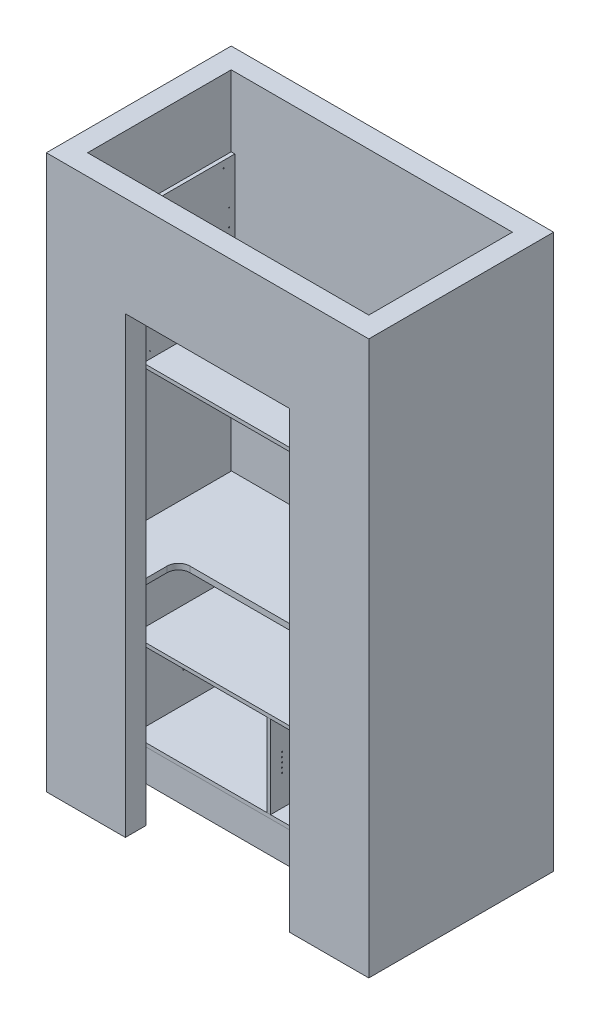
SolidWorks part; units mm, degrees
ref_plane "Front" through (0, 0, 0) normal (0, 0, 1) x (1, 0, 0)
ref_plane "Top" through (0, 0, 0) normal (0, 1, 0) x (1, 0, 0)
ref_plane "Right" through (0, 0, 0) normal (1, 0, 0) x (0, 0, -1)
sketch "Sketch1" plane through (0, 0, 0) normal (0, 1, 0) x (1, 0, 0)
  line L0 (-90, 90) -> (1317.5, 90)
  line L1 (0, 0) -> (1227.5, 0)
  line L2 (0, 0) -> (0, -627)
  line L3 (0, -627) -> (255, -627)
  line L4 (1227.5, 0) -> (1227.5, -627)
  line L5 (1317.5, 90) -> (1317.5, -717)
  line L6 (-90, -717) -> (255, -717)
  line L7 (-90, 90) -> (-90, -717)
  line L8 (255, -627) -> (255, -717)
  line L9 (972.5, -627) -> (972.5, -717)
  line L10 (972.5, -717) -> (1317.5, -717)
  line L11 (972.5, -627) -> (1227.5, -627)
  line L12 (-90, -717) -> (1317.5, -717) construction
  line L13 (255, -627) -> (972.5, -627)
  line L14 (0, -627) -> (1227.5, -627) construction
  line L15 (255, -717) -> (972.5, -717)
  dimension "D1" = 1227.5
  dimension "D2" = 627
  dimension "D4" = 255
  dimension "D5" = 255
  dimension "D3" = 90
extrude "Boss-Extrude1" add sketch "Sketch1" along normal blind 2416 contours L11 L9 L10 L5 L0 L7 L6 L8 L3 L2 L1 L4 | L8 L15 L9 L13 region at (613.75, 0, -73.7756) region at (613.75, 0, 672)
sketch "Sketch2" plane through (0, 0, 717) normal (0, 0, 1) x (1, 0, 0)
  line L0 (-90, 0) -> (1317.5, 0) construction
  line L1 (255, 0) -> (972.5, 0)
  line L2 (255, 0) -> (255, 1980)
  line L3 (255, 1980) -> (972.5, 1980)
  line L4 (972.5, 0) -> (972.5, 1980)
  line L5 (0, 2416) -> (0, 0) construction
  line L6 (1227.5, 2416) -> (1227.5, 0) construction
  dimension "D1" = 255
  dimension "D2" = 255
  dimension "D3" = 1980
  dimension "D4" = 717.5
extrude "Cut-Extrude1" cut sketch "Sketch2" against normal blind 100
sketch "Sketch4" plane through (0, 0, 0) normal (0, 0, 1) x (1, 0, 0)
  line L0 (1227.5, 2416) -> (1227.5, 0) construction
  line L5 (0, 120) -> (1227.5, 120)
  line L7 (16, 136) -> (1211.5, 136)
  line L9 (16, 513.5) -> (605.75, 513.5)
  line L11 (16, 497.5) -> (605.75, 497.5)
  line L13 (16, 875) -> (1211.5, 875)
  line L15 (16, 900) -> (1211.5, 900)
  line L21 (16, 1500) -> (1211.5, 1500)
  line L23 (16, 1516) -> (1211.5, 1516)
  line L25 (16, 1766) -> (1211.5, 1766)
  line L27 (16, 1782) -> (1211.5, 1782)
  line L37 (621.75, 513.5) -> (1211.5, 513.5)
  line L38 (621.75, 497.5) -> (1211.5, 497.5)
  line L39 (16, 1500) -> (0, 1500)
  line L40 (0, 120) -> (16, 120)
  line L41 (0, 120) -> (0, 2320)
  line L42 (598, 120) -> (613.75, 120)
  line L43 (605.75, 136) -> (605.75, 875)
  line L44 (605.75, 875) -> (614, 875)
  line L46 (614, 875) -> (621.75, 875)
  line L48 (613.75, 120) -> (630, 120)
  line L49 (621.75, 875) -> (621.75, 136)
  line L50 (0, 2320) -> (16, 2320)
  line L51 (16, 120) -> (16, 2320)
  line L52 (1211.5, 1500) -> (1227.5, 1500)
  line L54 (1227.5, 2320) -> (1227.5, 120)
  line L56 (1211.5, 2320) -> (1211.5, 120)
  line L57 (613.75, 136) -> (613.75, 171.2625) construction
  line L58 (1211.5, 2320) -> (1227.5, 2320)
  line L59 (-90, 0) -> (255, 0) construction
  line L60 (310.875, 513.5) -> (310.875, 875) construction
  line L61 (310.875, 497.5) -> (310.875, 136) construction
  dimension "D2" = 120
  dimension "D4" = 16
  dimension "D5" = 16
  dimension "D6" = 8
  dimension "D3" = 25
  dimension "D7" = 1500
  dimension "D8" = 250
  dimension "D9" = 16
  dimension "D10" = 2200
  dimension "D11" = 16
  dimension "D12" = 16
  dimension "D13" = 16
  dimension "D14" = 16
  dimension "D15" = 900
sketch "Sketch6" plane through (0, 0, 0) normal (0, 0, 1) x (1, 0, 0)
  line L0 (0, 120) -> (0, 2320) construction
  line L13 (16, 875) -> (0, 875)
  line L14 (16, 875) -> (16, 136)
  line L15 (16, 136) -> (0, 136)
  line L16 (0, 875) -> (0, 136)
  line L17 (16, 136) -> (1211.5, 136) construction
  line L18 (1227.5, 2320) -> (1227.5, 120) construction
  line L19 (1211.5, 875) -> (1227.5, 875)
  line L20 (1211.5, 875) -> (1211.5, 136)
  line L21 (1211.5, 136) -> (1227.5, 136)
  line L22 (1227.5, 875) -> (1227.5, 136)
  line L24 (605.75, 497.5) -> (621.75, 497.5)
  line L25 (605.75, 497.5) -> (605.75, 136)
  line L26 (605.75, 136) -> (621.75, 136)
  line L27 (621.75, 497.5) -> (621.75, 136)
extrude "Boss-Extrude2" add sketch "Sketch6" along normal blind 450 separate body
sketch "Sketch7" plane through (0, 0, 0) normal (0, 0, 1) x (1, 0, 0)
  line L0 (1227.5, 2320) -> (1227.5, 120) construction
  line L1 (0, 120) -> (1227.5, 120)
  line L2 (0, 120) -> (0, 136)
  line L3 (0, 136) -> (1227.5, 136)
  line L4 (1227.5, 120) -> (1227.5, 136)
  line L6 (16, 497.5) -> (16, 513.5)
  line L7 (16, 513.5) -> (1211.5, 513.5)
  line L9 (16, 497.5) -> (1211.5, 497.5)
  line L12 (1211.5, 497.5) -> (1211.5, 513.5)
  line L13 (0, 875) -> (1227.5, 875)
  line L14 (0, 875) -> (0, 900)
  line L15 (0, 900) -> (1227.5, 900)
  line L16 (1227.5, 875) -> (1227.5, 900)
  line L17 (16, 900) -> (1211.5, 900) construction
  line L19 (1211.5, 2320) -> (1211.5, 120) construction
  line L20 (16, 120) -> (16, 2320) construction
extrude "Boss-Extrude3" add sketch "Sketch7" along normal blind 450 separate body
sketch "Sketch8" plane through (0, 0, 0) normal (0, 0, 1) x (1, 0, 0)
  line L0 (0, 120) -> (0, 2320) construction
  line L1 (16, 1516) -> (0, 1516)
  line L2 (16, 1516) -> (16, 2106)
  line L3 (16, 2106) -> (0, 2106)
  line L4 (0, 1516) -> (0, 2106)
  line L5 (1227.5, 2320) -> (1227.5, 120) construction
  line L6 (1211.5, 1516) -> (1227.5, 1516)
  line L7 (1211.5, 1516) -> (1211.5, 2106)
  line L8 (1211.5, 2106) -> (1227.5, 2106)
  line L9 (1227.5, 1516) -> (1227.5, 2106)
  line L10 (16, 120) -> (16, 2320) construction
  dimension "D1" = 590
extrude "Boss-Extrude4" add sketch "Sketch8" along normal blind 400 separate body
sketch "Sketch9" plane through (0, 0, 0) normal (0, 0, 1) x (1, 0, 0)
  line L0 (1226.5, 1516) -> (1226.5, 1500)
  line L1 (16, 1782) -> (1211.5, 1782)
  line L2 (16, 1782) -> (16, 1766)
  line L3 (16, 1766) -> (1211.5, 1766)
  line L4 (1211.5, 1782) -> (1211.5, 1766)
  line L5 (1, 1516) -> (1226.5, 1516)
  line L6 (0, 1516) -> (0, 1500) construction
  line L7 (1, 1500) -> (1226.5, 1500)
  line L8 (1227.5, 1516) -> (1227.5, 1500) construction
  line L9 (1, 1516) -> (1, 1500)
  dimension "D1" = 1
  dimension "D2" = 1
extrude "Boss-Extrude5" add sketch "Sketch9" along normal blind 400 separate body
sketch "Sketch11" plane through (0, 900, 0) normal (0, 1, 0) x (1, 0, 0)
  line L0 (0, -450) -> (0, -627)
  line L1 (0, -627) -> (220, -627)
  line L2 (0, -627) -> (1227.5, -627) construction
  line L3 (220, -627) -> (220, -450)
  line L4 (1227.5, -450) -> (0, -450) construction
  line L5 (613.75, 90) -> (613.75, 254.9806) construction
  line L6 (-90, 90) -> (1317.5, 90) construction
  line L7 (0, -450) -> (220, -450)
  line L8 (1227.5, -450) -> (1007.5, -450)
  line L9 (1007.5, -627) -> (1007.5, -450)
  line L10 (1227.5, -627) -> (1007.5, -627)
  line L11 (1227.5, -450) -> (1227.5, -627)
  dimension "D1" = 220
extrude "Boss-Extrude6" add sketch "Sketch11" against normal up to surface (25 mm away) up to face at (613.75, 875, 225)
fillet "Fillet1" radius 50 2 edges at (220, 887.5, 450) (1007.5, 887.5, 450)
sketch "Sketch18" plane through (0, 120, 0) normal (0, -1, 0) x (1, 0, 0)
  line L0 (16, 0) -> (1211.5, 0) construction
  line L1 (0, 627) -> (1.25, 627)
  line L2 (0, 627) -> (0, 0)
  line L3 (0, 0) -> (1.25, 0)
  line L4 (1.25, 627) -> (1.25, 0)
  line L5 (1.25, 73.7952) -> (1226.25, 73.7952) construction
  line L6 (1227.5, 627) -> (1226.25, 627)
  line L7 (1227.5, 627) -> (1227.5, 0)
  line L8 (1227.5, 0) -> (1226.25, 0)
  line L9 (1226.25, 627) -> (1226.25, 0)
  line L10 (613.75, 73.7952) -> (613.75, -90) construction
  line L11 (-90, -90) -> (1317.5, -90) construction
  dimension "D1" = 1225
extrude "Cut-Extrude5" cut sketch "Sketch18" against normal through all
hole_wizard "Ø2.0 (2) Diameter Hole1" positions "Sketch20" profile "Sketch21" hole size "Ø2.0" standard "ISO"
sketch "Sketch20" plane through (0, 120, 0) normal (0, -1, 0) x (-1, 0, 0)
  line L1 (-645.75, -32) -> (-581.75, -32)
  line L2 (-645.75, -32) -> (-645.75, -96)
  line L3 (-645.75, -96) -> (-581.75, -96)
  line L4 (-581.75, -32) -> (-581.75, -96)
  line L7 (-613.75, -32) -> (-613.75, 0) construction
  line L8 (-1.25, 0) -> (-1226.25, 0) construction
  line L10 (0, 0) -> (-1227.5, 0) construction
  line L12 (-1176.25, -336.5) -> (-1112.25, -336.5)
  line L13 (-1176.25, -336.5) -> (-1176.25, -400.5)
  line L14 (-1176.25, -400.5) -> (-1112.25, -400.5)
  line L15 (-1112.25, -336.5) -> (-1112.25, -400.5)
  line L17 (-645.75, -336.5) -> (-581.75, -336.5)
  line L18 (-645.75, -336.5) -> (-645.75, -400.5)
  line L19 (-645.75, -400.5) -> (-581.75, -400.5)
  line L20 (-581.75, -336.5) -> (-581.75, -400.5)
  line L22 (-115.25, -336.5) -> (-51.25, -336.5)
  line L23 (-115.25, -336.5) -> (-115.25, -400.5)
  line L24 (-115.25, -400.5) -> (-51.25, -400.5)
  line L25 (-51.25, -336.5) -> (-51.25, -400.5)
  line L26 (-1226.25, -450) -> (-1226.25, 0) construction
  line L27 (-1.25, 0) -> (-1.25, -450) construction
  line L28 (-270, -450) -> (-957.5, -450) construction
  point P0 (-645.75, -32)
  point P2 (-581.75, -32)
  point P4 (-581.75, -96)
  point P6 (-645.75, -96)
  point P82 (-645.75, -400.5)
  point P84 (-645.75, -336.5)
  point P86 (-581.75, -336.5)
  point P88 (-581.75, -400.5)
  point P90 (-51.25, -400.5)
  point P92 (-51.25, -336.5)
  point P94 (-115.25, -336.5)
  point P96 (-115.25, -400.5)
  point P98 (-1176.25, -336.5)
  point P100 (-1112.25, -336.5)
  point P102 (-1112.25, -400.5)
  point P104 (-1176.25, -400.5)
  dimension "D1" = 50
  dimension "D2" = 64
  dimension "D3" = 50
  dimension "D4" = 49.5
  dimension "D5" = 64
  dimension "D6" = 32
sketch "Sketch21" plane through (645.75, 120, 32) normal (1, 0, 0) x (0, 0, -1)
  line L0 (0, 0) -> (0, 10.6009)
  line L1 (0, 10.6009) -> (1, 10)
  line L2 (1, 10) -> (1, 0)
  line L5 (1, 0) -> (0, 0)
  line L10 (0, 10.6009) -> (-1, 10) construction
  line L11 (0, -6.35) -> (0, 107.95) construction
  dimension "Hole Dia." = 2
  dimension "Hole Depth" = 10
  dimension "Drill Angle" = 118
hole_wizard "Ø2.0 (2) Diameter Hole2" positions "Sketch22" profile "Sketch23" hole size "Ø2.0" standard "ISO"
sketch "Sketch22" plane through (0, 120, 0) normal (0, -1, 0) x (-1, 0, 0)
  line L0 (-1219.5, -15) -> (-1219.5, -435) construction
  line L2 (-1227.5, 0) -> (-1227.5, -627) construction
  line L3 (0, 0) -> (0, -627) construction
  line L4 (-1.25, -450) -> (-1226.25, -450) construction
  line L5 (0, 0) -> (-1227.5, 0) construction
  line L6 (-613.75, -435) -> (-613.75, -450) construction
  line L7 (-270, -450) -> (-957.5, -450) construction
  point P0 (-1219.5, -435)
  point P2 (-1219.5, -225)
  point P4 (-1219.5, -15)
  point P6 (-613.75, -15)
  point P8 (-613.75, -225)
  point P10 (-613.75, -435)
  point P12 (-8, -15)
  point P14 (-8, -225)
  point P16 (-8, -435)
  dimension "D1" = 8
  dimension "D2" = 8
  dimension "D3" = 15
  dimension "D4" = 15
sketch "Sketch23" plane through (1219.5, 120, 435) normal (1, 0, 0) x (0, 0, -1)
  line L0 (0, 0) -> (0, 10.6009)
  line L1 (0, 10.6009) -> (1, 10)
  line L2 (1, 10) -> (1, 0)
  line L5 (1, 0) -> (0, 0)
  line L10 (0, 10.6009) -> (-1, 10) construction
  line L11 (0, -6.35) -> (0, 107.95) construction
  dimension "Hole Dia." = 2
  dimension "Hole Depth" = 10
  dimension "Drill Angle" = 118
sketch "Sketch24" plane through (0, 120, 0) normal (0, -1, 0) x (1, 0, 0)
  circle A0 centre (8, 435) radius 2.5
  circle A1 centre (8, 225) radius 2.5
  circle A2 centre (8, 15) radius 2.5
  circle A3 centre (613.75, 435) radius 2.5
  circle A4 centre (613.75, 225) radius 2.5
  circle A5 centre (613.75, 15) radius 2.5
  circle A6 centre (1219.5, 15) radius 2.5
  circle A7 centre (1219.5, 225) radius 2.5
  circle A8 centre (1219.5, 435) radius 2.5
  dimension "D1" = 5
extrude "Cut-Extrude6" cut sketch "Sketch24" against normal blind 1
sketch "Sketch25" plane through (16, 0, 0) normal (1, 0, 0) x (0, 0, -1)
  line L0 (-450, 497.5) -> (0, 497.5) construction
  line L1 (-450, 497.5) -> (0, 497.5) construction
  line L2 (-400, 497.5) -> (-50, 497.5) construction
  circle A0 centre (-400, 497.5) radius 2.5
  circle A1 centre (-50, 497.5) radius 2.5
  circle A2 centre (-225, 497.5) radius 2.5
  dimension "D1" = 5
  dimension "D2" = 350
extrude "Cut-Extrude7" cut sketch "Sketch25" against normal through all both and the other way through all
sketch "Sketch26" plane through (16, 0, 0) normal (1, 0, 0) x (0, 0, -1)
  line L0 (-400, 497.5) -> (-50, 497.5) construction
  circle A0 centre (-400, 308.75) radius 2.5
  circle A1 centre (-225, 308.75) radius 2.5
  circle A2 centre (-50, 308.75) radius 2.5
  circle A3 centre (-400, 497.5) radius 2.5 construction
  circle A4 centre (-400, 328.75) radius 2.5
  circle A5 centre (-225, 328.75) radius 2.5
  circle A6 centre (-50, 328.75) radius 2.5
  circle A7 centre (-400, 348.75) radius 2.5
  circle A8 centre (-225, 348.75) radius 2.5
  circle A9 centre (-50, 348.75) radius 2.5
  circle A10 centre (-400, 288.75) radius 2.5
  circle A11 centre (-225, 288.75) radius 2.5
  circle A12 centre (-50, 288.75) radius 2.5
  circle A13 centre (-400, 268.75) radius 2.5
  circle A14 centre (-225, 268.75) radius 2.5
  circle A15 centre (-50, 268.75) radius 2.5
  dimension "D1" = 188.75
  dimension "D2" = 3
  dimension "D3" = 3
extrude "Cut-Extrude8" cut sketch "Sketch26" against normal through all both and the other way through all
sketch "Sketch34" plane through (0, 497.5, 0) normal (0, -1, 0) x (1, 0, 0)
  line L0 (16, 450) -> (16, 0) construction
  line L1 (16, 403) -> (39.6625, 403)
  line L2 (16, 403) -> (16, 397)
  line L3 (16, 397) -> (39.6625, 397)
  line L4 (41.25, 401.4125) -> (41.25, 398.5875)
  line L15 (16, 400) -> (41.25, 400) construction
  line L16 (1.25, 0) -> (1.25, 450) construction
  line L17 (0, 400) -> (16, 400) construction
  line L18 (16, 228) -> (39.6625, 228)
  line L19 (16, 228) -> (16, 222)
  line L20 (16, 222) -> (39.6625, 222)
  line L21 (41.25, 226.4125) -> (41.25, 223.5875)
  line L22 (16, 225) -> (41.25, 225) construction
  line L23 (16, 53) -> (39.6625, 53)
  line L24 (16, 53) -> (16, 47)
  line L25 (16, 47) -> (39.6625, 47)
  line L26 (41.25, 51.4125) -> (41.25, 48.5875)
  line L27 (16, 50) -> (41.25, 50) construction
  line L28 (613.75, 435) -> (613.75, 225) construction
  line L29 (1211.5, 50) -> (1186.25, 50) construction
  line L30 (1211.5, 225) -> (1186.25, 225) construction
  line L31 (1211.5, 400) -> (1186.25, 400) construction
  line L32 (1186.25, 51.4125) -> (1186.25, 48.5875)
  line L33 (1211.5, 47) -> (1187.8375, 47)
  line L34 (1211.5, 53) -> (1211.5, 47)
  line L35 (1211.5, 53) -> (1187.8375, 53)
  line L36 (1186.25, 226.4125) -> (1186.25, 223.5875)
  line L37 (1211.5, 222) -> (1187.8375, 222)
  line L38 (1211.5, 228) -> (1211.5, 222)
  line L39 (1211.5, 228) -> (1187.8375, 228)
  line L40 (1186.25, 401.4125) -> (1186.25, 398.5875)
  line L41 (1211.5, 397) -> (1187.8375, 397)
  line L42 (1211.5, 403) -> (1211.5, 397)
  line L43 (1211.5, 403) -> (1187.8375, 403)
  arc A0 (39.6625, 397) -> (41.25, 398.5875) centre (39.6625, 398.5875) ccw
  arc A1 (39.6625, 403) -> (41.25, 401.4125) centre (39.6625, 401.4125) cw
  arc A2 (39.6625, 222) -> (41.25, 223.5875) centre (39.6625, 223.5875) ccw
  arc A3 (39.6625, 228) -> (41.25, 226.4125) centre (39.6625, 226.4125) cw
  arc A4 (39.6625, 47) -> (41.25, 48.5875) centre (39.6625, 48.5875) ccw
  arc A5 (39.6625, 53) -> (41.25, 51.4125) centre (39.6625, 51.4125) cw
  arc A6 (1187.8375, 53) -> (1186.25, 51.4125) centre (1187.8375, 51.4125) ccw
  arc A7 (1187.8375, 47) -> (1186.25, 48.5875) centre (1187.8375, 48.5875) cw
  arc A8 (1187.8375, 228) -> (1186.25, 226.4125) centre (1187.8375, 226.4125) ccw
  arc A9 (1187.8375, 222) -> (1186.25, 223.5875) centre (1187.8375, 223.5875) cw
  arc A10 (1187.8375, 403) -> (1186.25, 401.4125) centre (1187.8375, 401.4125) ccw
  arc A11 (1187.8375, 397) -> (1186.25, 398.5875) centre (1187.8375, 398.5875) cw
  point P26 (41.25, 397)
  point P29 (41.25, 403)
  point P73 (1186.25, 403)
  point P74 (1186.25, 397)
  dimension "D3" = 1.5875
  dimension "D1" = 40
  dimension "D2" = 6
  dimension "D4" = 3
extrude "Cut-Extrude9" cut sketch "Sketch34" against normal blind 3
hole_wizard "Ø2.0 (2) Diameter Hole3" positions "Sketch35" profile "Sketch36" hole size "Ø2.0" standard "ISO"
sketch "Sketch35" plane through (621.75, 0, 0) normal (1, 0, 0) x (0, 0, -1)
  line L0 (-450, 136) -> (-450, 497.5) construction
  line L1 (-450, 497.5) -> (0, 497.5) construction
  line L2 (0, 875) -> (0, 136) construction
  point P0 (-400, 481.5)
  point P7 (-100, 481.5)
  dimension "D1" = 50
  dimension "D2" = 16
  dimension "D3" = 100
sketch "Sketch36" plane through (621.75, 481.5, 400) normal (0, 1, 0) x (0, 0, -1)
  line L0 (0, 0) -> (0, 18.6009)
  line L1 (0, 18.6009) -> (1, 18)
  line L2 (1, 18) -> (1, 0)
  line L5 (1, 0) -> (0, 0)
  line L10 (0, 18.6009) -> (-1, 18) construction
  line L11 (0, -6.35) -> (0, 107.95) construction
  dimension "Hole Dia." = 2
  dimension "Hole Depth" = 18
  dimension "Drill Angle" = 118
hole_wizard "Ø2.0 (2) Diameter Hole4" positions "Sketch37" profile "Sketch38" hole size "Ø2.0" standard "ISO" end condition through all
sketch "Sketch37" plane through (1317.5, 0, 0) normal (1, 0, 0) x (0, 0, -1)
  line L0 (-450, 136) -> (-450, 875) construction
  line L1 (0, 120) -> (0, 2320) construction
  line L2 (-450, 875) -> (0, 875) construction
  line L3 (-450, 136) -> (0, 136) construction
  point P0 (-425, 171)
  point P2 (-425, 471)
  point P4 (-425, 825)
  point P6 (-50, 825)
  point P10 (-50, 171)
  dimension "D1" = 25
  dimension "D2" = 50
  dimension "D3" = 50
  dimension "D4" = 35
  dimension "D5" = 300
sketch "Sketch38" plane through (1317.5, 171, 425) normal (0, 1, 0) x (0, 0, -1)
  line L0 (0, 0) -> (0, 1407.5)
  line L1 (0, 1407.5) -> (1, 1407.5)
  line L2 (1, 1407.5) -> (1, 0)
  line L5 (1, 0) -> (0, 0)
  line L11 (0, -6.35) -> (0, 107.95) construction
  dimension "Thru Hole Dia." = 2
  dimension "Thru Hole Depth" = 1407.5
sketch "Sketch39" plane through (16, 0, 0) normal (1, 0, 0) x (0, 0, -1)
  circle A0 centre (-425, 171) radius 2.5
  circle A1 centre (-50, 171) radius 2.5
  circle A2 centre (-425, 471) radius 2.5
  circle A3 centre (-425, 825) radius 2.5
  circle A4 centre (-50, 825) radius 2.5
  dimension "D1" = 5
extrude "Cut-Extrude10" cut sketch "Sketch39" against normal blind 1
sketch "Sketch40" plane through (1211.5, 0, 0) normal (-1, 0, 0) x (0, 0, 1)
  circle A1 centre (50, 825) radius 2.5
  circle A2 centre (50, 825) radius 2.5
  circle A3 centre (425, 825) radius 2.5
  circle A4 centre (425, 825) radius 2.5
  circle A5 centre (425, 471) radius 2.5
  circle A6 centre (425, 471) radius 2.5
  circle A7 centre (50, 171) radius 2.5
  circle A8 centre (50, 171) radius 2.5
  circle A9 centre (425, 171) radius 2.5
  circle A10 centre (425, 171) radius 2.5
  dimension "D1" = 0
  dimension "D2" = 0
  dimension "D3" = 0
  dimension "D4" = 0
  dimension "D5" = 0
extrude "Cut-Extrude11" cut sketch "Sketch40" against normal blind 1
sketch "Sketch41" plane through (0, 1782, 0) normal (0, 1, 0) x (1, 0, 0)
  line L0 (1211.5, -400) -> (16, -400) construction
  line L1 (16, 0) -> (17, 0)
  line L2 (16, 0) -> (16, -400)
  line L3 (16, -400) -> (17, -400)
  line L4 (17, 0) -> (17, -400)
  line L6 (1211.5, 0) -> (1210.5, 0)
  line L7 (1211.5, 0) -> (1211.5, -400)
  line L8 (1211.5, -400) -> (1210.5, -400)
  line L9 (1210.5, 0) -> (1210.5, -400)
  dimension "D1" = 1
  dimension "D2" = 1
extrude "Cut-Extrude12" cut sketch "Sketch41" against normal up to next (16 mm away)
hole_wizard "Ø2.0 (2) Diameter Hole5" positions "Sketch42" profile "Sketch43" hole size "Ø2.0" standard "ISO" end condition through all
sketch "Sketch42" plane through (0, 1500, 0) normal (0, -1, 0) x (-1, 0, 0)
  line L0 (-1227.5, -400) -> (-1227.5, 0) construction
  line L1 (0, -400) -> (0, 0) construction
  line L2 (-1, -400) -> (-1226.5, -400) construction
  line L3 (0, 0) -> (-16, 0) construction
  point P0 (-1219.5, -380)
  point P2 (-1219.5, -200)
  point P4 (-1219.5, -20)
  point P6 (-8, -380)
  point P8 (-8, -200)
  point P10 (-8, -20)
  dimension "D1" = 8
  dimension "D2" = 8
  dimension "D3" = 20
  dimension "D4" = 20
  dimension "D5" = 180
sketch "Sketch43" plane through (1219.5, 1500, 380) normal (1, 0, 0) x (0, 0, -1)
  line L0 (0, 0) -> (0, 916)
  line L1 (0, 916) -> (1, 916)
  line L2 (1, 916) -> (1, 0)
  line L5 (1, 0) -> (0, 0)
  line L11 (0, -6.35) -> (0, 107.95) construction
  dimension "Thru Hole Dia." = 2
  dimension "Thru Hole Depth" = 916
sketch "Sketch44" plane through (0, 1500, 0) normal (0, -1, 0) x (1, 0, 0)
  circle A0 centre (8, 380) radius 2.5
  circle A1 centre (8, 200) radius 2.5
  circle A2 centre (8, 20) radius 2.5
  circle A3 centre (1219.5, 20) radius 2.5
  circle A4 centre (1219.5, 200) radius 2.5
  circle A5 centre (1219.5, 380) radius 2.5
  dimension "D1" = 5
extrude "Cut-Extrude13" cut sketch "Sketch44" against normal blind 1
hole_wizard "Ø5.0 (5) Diameter Hole1" positions "Sketch45" profile "Sketch46" hole size "Ø5.0" standard "ISO" end condition through all
sketch "Sketch45" plane through (1227.5, 0, 0) normal (1, 0, 0) x (0, 0, -1)
  line L0 (-400, 1766) -> (0, 1766) construction
  line L1 (-400, 1516) -> (-400, 2106) construction
  line L2 (0, 120) -> (0, 2320) construction
  point P0 (-375, 1766)
  point P4 (-200, 1766)
  point P6 (-25, 1766)
  point P8 (-375, 1841)
  point P10 (-200, 1841)
  point P12 (-25, 1841)
  point P14 (-375, 1916)
  point P16 (-200, 1916)
  point P18 (-25, 1916)
  dimension "D1" = 25
  dimension "D2" = 25
  dimension "D3" = 75
  dimension "D4" = 75
sketch "Sketch46" plane through (1227.5, 1766, 375) normal (0, 1, 0) x (0, 0, -1)
  line L0 (0, 0) -> (0, 1317.5)
  line L1 (0, 1317.5) -> (2.5, 1317.5)
  line L2 (2.5, 1317.5) -> (2.5, 0)
  line L5 (2.5, 0) -> (0, 0)
  line L11 (0, -6.35) -> (0, 107.95) construction
  dimension "Thru Hole Dia." = 5
  dimension "Thru Hole Depth" = 1317.5
hole_wizard "Ø2.0 (2) Diameter Hole6" positions "Sketch48" profile "Sketch49" hole size "Ø2.0" standard "ISO" end condition through all
sketch "Sketch48" plane through (1227.5, 0, 0) normal (1, 0, 0) x (0, 0, -1)
  line L0 (-400, 1516) -> (0, 1516) construction
  line L1 (-400, 1516) -> (-400, 2106) construction
  line L2 (0, 120) -> (0, 2320) construction
  line L3 (-400, 2106) -> (0, 2106) construction
  circle A0 centre (-375, 1766) radius 2.5 construction
  point P0 (-370, 1546)
  point P2 (-370, 2076)
  point P4 (-370, 1801)
  point P6 (-50, 1546)
  point P8 (-50, 1801)
  point P10 (-50, 2076)
  dimension "D1" = 30
  dimension "D2" = 30
  dimension "D3" = 50
  dimension "D4" = 35
  dimension "D5" = 30
sketch "Sketch49" plane through (1227.5, 1546, 370) normal (0, 1, 0) x (0, 0, -1)
  line L0 (0, 0) -> (0, 1317.5)
  line L1 (0, 1317.5) -> (1, 1317.5)
  line L2 (1, 1317.5) -> (1, 0)
  line L5 (1, 0) -> (0, 0)
  line L11 (0, -6.35) -> (0, 107.95) construction
  dimension "Thru Hole Dia." = 2
  dimension "Thru Hole Depth" = 1317.5
sketch "Sketch50" plane through (16, 0, 0) normal (1, 0, 0) x (0, 0, -1)
  circle A0 centre (-370, 2076) radius 2.5
  circle A1 centre (-50, 2076) radius 2.5
  circle A2 centre (-50, 1801) radius 2.5
  circle A3 centre (-370, 1801) radius 2.5
  circle A4 centre (-370, 1546) radius 2.5
  circle A5 centre (-50, 1546) radius 2.5
  dimension "D1" = 5
extrude "Cut-Extrude14" cut sketch "Sketch50" against normal blind 1
sketch "Sketch51" plane through (1211.5, 0, 0) normal (-1, 0, 0) x (0, 0, 1)
  circle A1 centre (370, 1546) radius 2.5
  circle A2 centre (370, 1546) radius 2.5
  circle A3 centre (370, 1801) radius 2.5
  circle A4 centre (370, 1801) radius 2.5
  circle A5 centre (50, 1801) radius 2.5
  circle A6 centre (50, 1801) radius 2.5
  circle A7 centre (50, 2076) radius 2.5
  circle A8 centre (50, 2076) radius 2.5
  circle A9 centre (370, 2076) radius 2.5
  circle A10 centre (370, 2076) radius 2.5
  circle A11 centre (50, 1546) radius 2.5
  circle A12 centre (50, 1546) radius 2.5
  dimension "D1" = 0
  dimension "D2" = 0
  dimension "D3" = 0
  dimension "D4" = 0
  dimension "D5" = 0
  dimension "D6" = 0
extrude "Cut-Extrude15" cut sketch "Sketch51" against normal blind 1
sketch "Sketch52" plane through (0, 1766, 0) normal (0, -1, 0) x (1, 0, 0)
  line L0 (17, 0) -> (17, 400) construction
  line L1 (17, 378) -> (38.4125, 378)
  line L2 (17, 378) -> (17, 372)
  line L3 (17, 372) -> (38.4125, 372)
  line L4 (40, 376.4125) -> (40, 373.5875)
  line L5 (17, 375) -> (40, 375) construction
  line L6 (0, 400) -> (0, 0) construction
  line L7 (17, 400) -> (1210.5, 400) construction
  line L9 (613.75, 435) -> (613.75, -96.6075) construction
  line L13 (17, 203) -> (38.4125, 203)
  line L18 (17, 203) -> (17, 197)
  line L19 (17, 197) -> (38.4125, 197)
  line L20 (40, 201.4125) -> (40, 198.5875)
  line L21 (17, 200) -> (40, 200) construction
  line L22 (17, 28) -> (38.4125, 28)
  line L23 (17, 28) -> (17, 22)
  line L24 (17, 22) -> (38.4125, 22)
  line L25 (40, 26.4125) -> (40, 23.5875)
  line L26 (17, 25) -> (40, 25) construction
  line L27 (1210.5, 25) -> (1187.5, 25) construction
  line L28 (1210.5, 200) -> (1187.5, 200) construction
  line L29 (1210.5, 375) -> (1187.5, 375) construction
  line L30 (1187.5, 26.4125) -> (1187.5, 23.5875)
  line L31 (1210.5, 22) -> (1189.0875, 22)
  line L32 (1210.5, 28) -> (1210.5, 22)
  line L33 (1210.5, 28) -> (1189.0875, 28)
  line L34 (1187.5, 201.4125) -> (1187.5, 198.5875)
  line L35 (1210.5, 197) -> (1189.0875, 197)
  line L36 (1210.5, 203) -> (1210.5, 197)
  line L37 (1210.5, 203) -> (1189.0875, 203)
  line L38 (1187.5, 376.4125) -> (1187.5, 373.5875)
  line L39 (1210.5, 372) -> (1189.0875, 372)
  line L40 (1210.5, 378) -> (1210.5, 372)
  line L41 (1210.5, 378) -> (1189.0875, 378)
  arc A0 (38.4125, 372) -> (40, 373.5875) centre (38.4125, 373.5875) ccw
  arc A1 (38.4125, 378) -> (40, 376.4125) centre (38.4125, 376.4125) cw
  arc A6 (38.4125, 197) -> (40, 198.5875) centre (38.4125, 198.5875) ccw
  arc A7 (38.4125, 203) -> (40, 201.4125) centre (38.4125, 201.4125) cw
  arc A8 (38.4125, 22) -> (40, 23.5875) centre (38.4125, 23.5875) ccw
  arc A9 (38.4125, 28) -> (40, 26.4125) centre (38.4125, 26.4125) cw
  arc A10 (1189.0875, 28) -> (1187.5, 26.4125) centre (1189.0875, 26.4125) ccw
  arc A11 (1189.0875, 22) -> (1187.5, 23.5875) centre (1189.0875, 23.5875) cw
  arc A12 (1189.0875, 203) -> (1187.5, 201.4125) centre (1189.0875, 201.4125) ccw
  arc A13 (1189.0875, 197) -> (1187.5, 198.5875) centre (1189.0875, 198.5875) cw
  arc A14 (1189.0875, 378) -> (1187.5, 376.4125) centre (1189.0875, 376.4125) ccw
  arc A15 (1189.0875, 372) -> (1187.5, 373.5875) centre (1189.0875, 373.5875) cw
  dimension "D1" = 1.5875
  dimension "D2" = 6
  dimension "D3" = 40
  dimension "D4" = 25
  dimension "D5" = 3
extrude "Cut-Extrude16" cut sketch "Sketch52" against normal blind 3
sketch "Sketch54" plane through (0, 0, 450) normal (0, 0, 1) x (1, 0, 0)
  line L0 (1226.25, 120) -> (1226.25, 136) construction
  line L1 (1.25, 120) -> (1226.25, 120)
  line L2 (1.25, 120) -> (1.25, -19)
  line L3 (1.25, -19) -> (1226.25, -19)
  line L4 (1226.25, 120) -> (1226.25, -19)
  dimension "D1" = 139
extrude "Boss-Extrude7" add sketch "Sketch54" against normal blind 16 separate body
sketch "Sketch55" plane through (0, 0, 434) normal (0, 0, -1) x (-1, 0, 0)
  line L0 (-1226.25, 120) -> (-1.25, 120) construction
  line L1 (-1169.25, 80) -> (-1119.25, 80)
  line L3 (-1169.25, 77) -> (-1119.25, 77)
  line L5 (-108.25, 80) -> (-58.25, 80)
  line L7 (-108.25, 77) -> (-58.25, 77)
  line L8 (-1144.25, 80) -> (-1144.25, -56.6281) construction
  line L9 (-1226.25, -19) -> (-1226.25, 120) construction
  line L10 (-83.25, 80) -> (-83.25, 123.5184) construction
  line L11 (-1.25, 120) -> (-1.25, -19) construction
  arc A0 (-1169.25, 80) -> (-1169.25, 77) centre (-1169.25, 78.5) ccw
  arc A1 (-1119.25, 77) -> (-1119.25, 80) centre (-1119.25, 78.5) ccw
  arc A2 (-108.25, 80) -> (-108.25, 77) centre (-108.25, 78.5) ccw
  arc A3 (-58.25, 77) -> (-58.25, 80) centre (-58.25, 78.5) ccw
  dimension "D1" = 3
  dimension "D2" = 50
  dimension "D3" = 40
  dimension "D4" = 3
  dimension "D5" = 82
  dimension "D6" = 82
extrude "Cut-Extrude17" cut sketch "Sketch55" against normal blind 8
delete or keep bodies "Body-Delete/Keep 1" [suppressed] type delete bodies bodies 102
delete or keep bodies "Body-Delete/Keep 2" [suppressed] type keep bodies bodies 124
delete or keep bodies "Body-Delete/Keep 3" [suppressed] type keep bodies bodies 127
delete or keep bodies "Body-Delete/Keep 4" [suppressed] type keep bodies bodies 147
delete or keep bodies "Body-Delete/Keep 5" [suppressed] type keep bodies bodies 148
delete or keep bodies "Body-Delete/Keep 6" [suppressed] type keep bodies bodies 151
delete or keep bodies "Body-Delete/Keep 7" [suppressed] type keep bodies bodies 152
delete or keep bodies "Body-Delete/Keep 8" [suppressed] type keep bodies bodies 157
delete or keep bodies "Body-Delete/Keep 9" [suppressed] type keep bodies bodies 163
delete or keep bodies "Body-Delete/Keep 10" [suppressed] type keep bodies bodies 164
delete or keep bodies "Body-Delete/Keep 11" [suppressed] type keep bodies bodies 165
delete or keep bodies "Body-Delete/Keep 12" [suppressed] type keep bodies bodies 167
